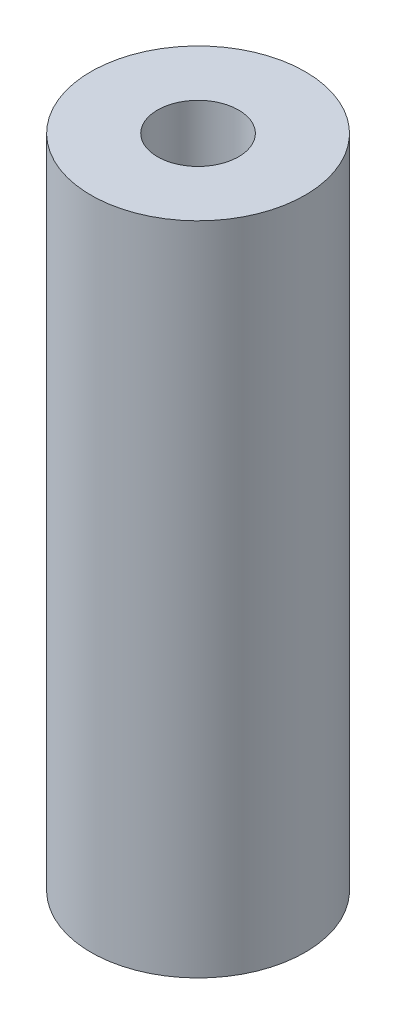
SolidWorks part; units mm, degrees
ref_plane "Front Plane" through (0, 0, 0) normal (0, 0, 1) x (1, 0, 0)
ref_plane "Top Plane" through (0, 0, 0) normal (0, 1, 0) x (1, 0, 0)
ref_plane "Right Plane" through (0, 0, 0) normal (1, 0, 0) x (0, 0, -1)
sketch "Sketch1" plane through (0, 0, 0) normal (0, 1, 0) x (1, 0, 0)
  circle A0 centre (0, 0) radius 3.1115
  circle A1 centre (0, 0) radius 1.1781
  dimension "D1" = 6.223
extrude "Boss-Extrude1" add sketch "Sketch1" along normal blind 19.05
